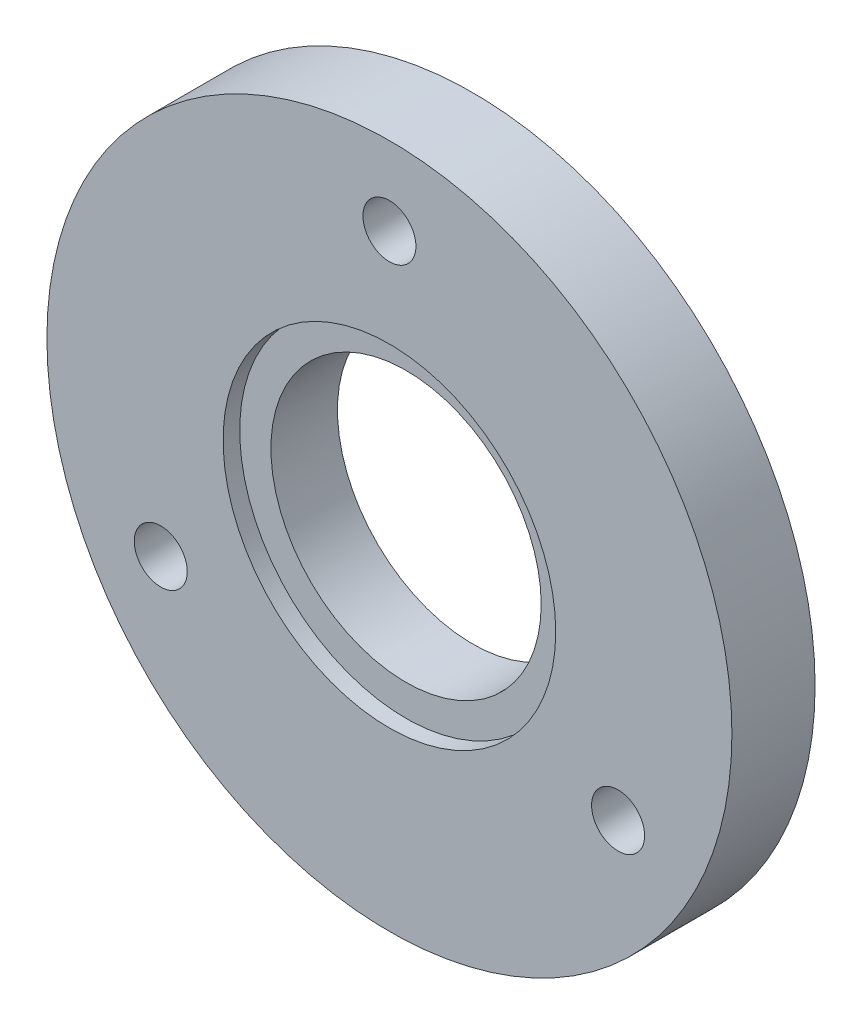
SolidWorks part; units mm, degrees
ref_plane "Front Plane" through (0, 0, 0) normal (0, 0, 1) x (1, 0, 0)
ref_plane "Top Plane" through (0, 0, 0) normal (0, 1, 0) x (1, 0, 0)
ref_plane "Right Plane" through (0, 0, 0) normal (1, 0, 0) x (0, 0, -1)
sketch "Sketch1" plane through (0, 0, 0) normal (0, 0, 1) x (1, 0, 0)
  line L0 (0, 25.4) -> (-21.997, -12.7) construction
  line L1 (-21.997, -12.7) -> (21.997, -12.7) construction
  line L2 (21.997, -12.7) -> (0, 25.4) construction
  circle A0 centre (0, 0) radius 13
  circle A1 centre (0, 0) radius 16 construction
  circle A3 centre (0, 0) radius 32.95
  circle A4 centre (0, 0) radius 25.4 construction
  circle A5 centre (0, 25.4) radius 2.55
  circle A6 centre (-21.997, -12.7) radius 2.55
  circle A7 centre (21.997, -12.7) radius 2.55
  circle A8 centre (0, 0) radius 16
  dimension "D1" = 26
  dimension "D2" = 32
  dimension "D3" = 5
  dimension "D5" = 50.8
  dimension "D6" = 5.1
  dimension "D7" = 5.1
  dimension "D8" = 5.1
extrude "Boss-Extrude1" add sketch "Sketch1" against normal blind 8 contours A8 A0 | A8 region at (-32.018, 0, 0) region at (-15.5475, 0, 0)
extrude "Boss-Extrude4" add sketch "Sketch1<7>" against normal blind 6.35 contours A3 A7 A6 A5 region at (-32.018, 0, 0)
sketch "Sketch1<7>" plane through (0, 0, 0) normal (0, 0, 1) x (1, 0, 0) same geometry as "Sketch1"
extrude "Cut-Extrude1" cut sketch "Sketch1<10>" against normal blind 1.6 contours A8 A0 region at (-15.5475, 0, 0)
sketch "Sketch1<10>" plane through (0, 0, 0) normal (0, 0, 1) x (1, 0, 0) same geometry as "Sketch1"
